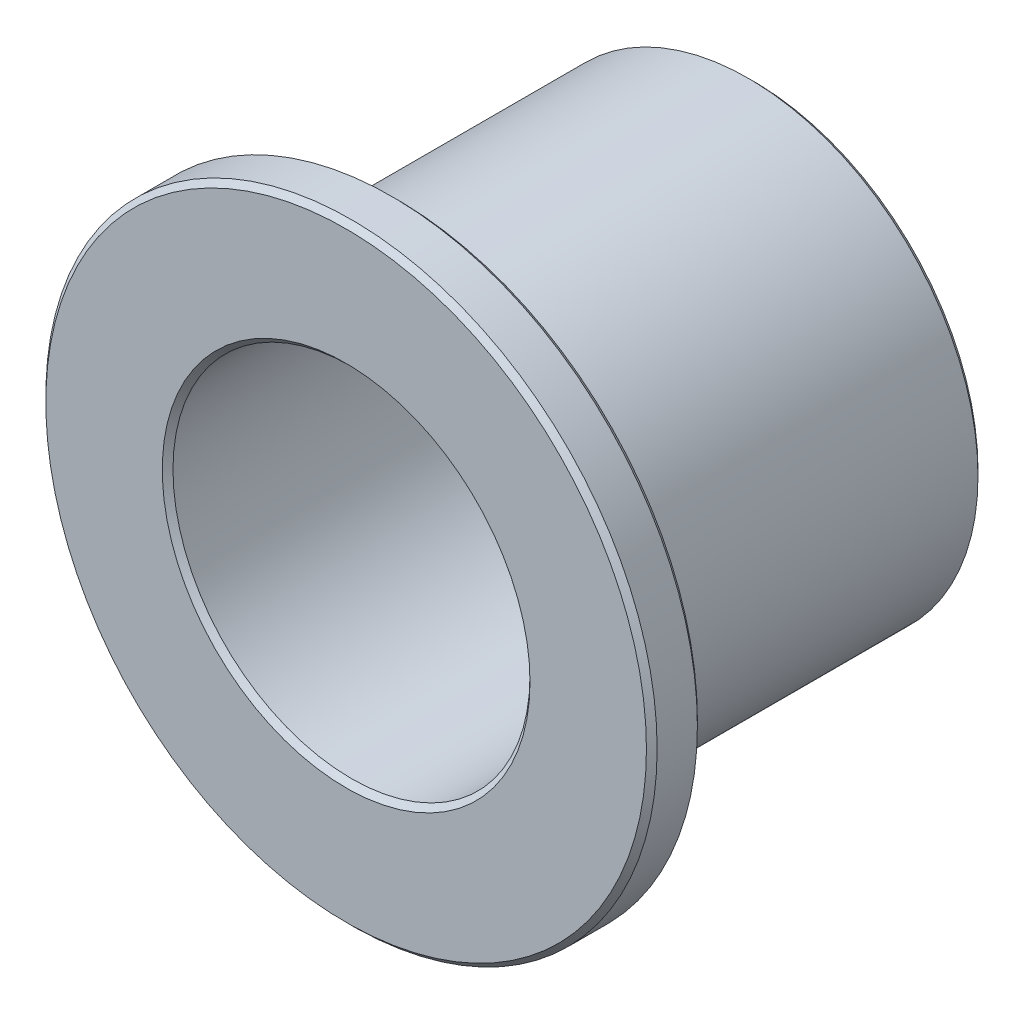
SolidWorks part; units mm, degrees
ref_plane "Front" through (0, 0, 0) normal (0, 0, 1) x (1, 0, 0)
ref_plane "Top" through (0, 0, 0) normal (0, 1, 0) x (1, 0, 0)
ref_plane "Right" through (0, 0, 0) normal (1, 0, 0) x (0, 0, -1)
sketch "Sketch1" plane through (0, 0, 0) normal (0, 0, 1) x (1, 0, 0)
  circle A0 centre (0, 0) radius 11.1252
  circle A1 centre (0, 0) radius 14.3129
  circle A2 centre (0, 0) radius 19.05
  dimension "ID" = 22.2504
  dimension "OD" = 28.6258
  dimension "Flange OD" = 38.1
sketch "Sketch2" plane through (0, 0, 0) normal (1, 0, 0) x (0, 0, -1)
  line L0 (-12.7, -19.05) -> (12.7, -19.05) construction
  line L1 (0, 19.05) -> (0, -19.05) construction
  line L3 (-9.525, 14.3129) -> (12.7, 14.3129) construction
  point P3 (0, -19.05)
  point P7 (0, 14.3129)
  point P9 (-9.525, -19.05)
  point P10 (-12.7, 19.05)
  point P23 (0, 19.05)
  dimension "Flange Thickness" = 3.175
  dimension "Length" = 25.4
sketch "Sketch3" plane through (0, 0, 0) normal (0, 0, 1) x (1, 0, 0)
  circle A0 centre (0, 0) radius 19.05 construction
  circle A1 centre (0, 0) radius 19.05
  circle A2 centre (0, 0) radius 11.1252 construction
  circle A3 centre (0, 0) radius 11.1252
extrude "Boss-Extrude1" add sketch "Sketch3" against normal up to vertex (-9.525 mm away) from vertex up to point (0, -19.05, 9.525) starting at point (0, -19.05, 12.7)
sketch "Sketch4" plane through (0, 0, 0) normal (0, 0, 1) x (1, 0, 0)
  circle A0 centre (0, 0) radius 11.1252 construction
  circle A1 centre (0, 0) radius 14.3129 construction
  circle A2 centre (0, 0) radius 11.1252
  circle A3 centre (0, 0) radius 14.3129
extrude "Boss-Extrude2" add sketch "Sketch4" against normal up to vertex (12.7 mm away) from vertex up to point (0, 14.3129, -12.7) starting at point (0, -19.05, 9.525)
chamfer "Chamfer1" distance 0.3338 angle 45 6 edges at (11.1252, 0, 12.7) (19.05, 0, 12.7) (19.05, 0, 9.525) (14.3129, 0, 9.525) (11.1252, 0, -12.7) (14.3129, 0, -12.7)
equation "\"D1@Chamfer1\"=\"ID@Sketch1\"*0.015"
